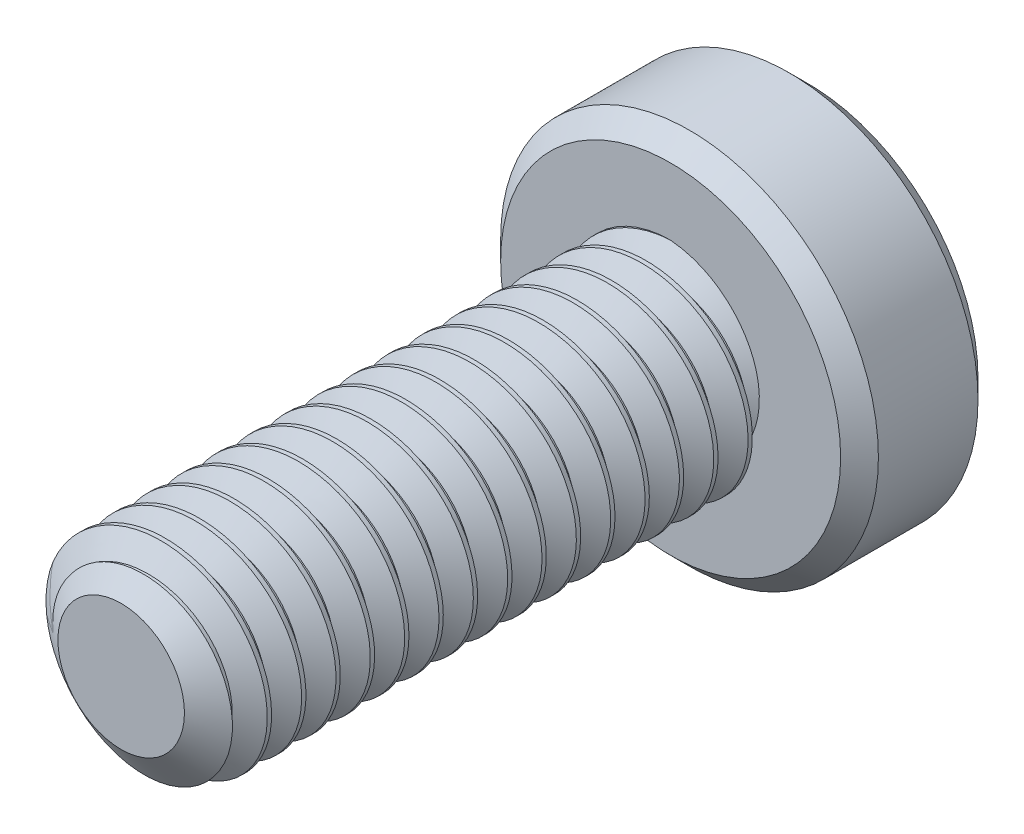
SolidWorks part; units mm, degrees
other "DetailItem1"
ref_plane "Front Plane" through (0, 0, 0) normal (0, 0, 1) x (1, 0, 0)
ref_plane "Top Plane" through (0, 0, 0) normal (0, 1, 0) x (1, 0, 0)
ref_plane "Right Plane" through (0, 0, 0) normal (1, 0, 0) x (0, 0, -1)
sketch "Sketch1" plane through (0, 0, 0) normal (0, 0, 1) x (1, 0, 0)
  circle A0 centre (0, 0) radius 1.5
  dimension "OD" = 3
extrude "Extrude1" add sketch "Sketch1" against normal blind 8
sketch "Sketch2" plane through (0, 0, 0) normal (0, 0, 1) x (1, 0, 0)
  circle A0 centre (0, 0) radius 1.5 construction
  circle A1 centre (0, 0) radius 1.5
curve "Helix/Spiral1" pitch 0.5 height 8.5 radius 1.5 centre (0, 0, 0) axis (0, 0, -1) start towards (0, 1, 0) parameters "pitch"=0.5
sketch "Sketch3" plane through (0, 0, 0) normal (1, 0, 0) x (0, 0, -1)
  line L0 (-0.4375, 1.5) -> (-0.25, 1.1752)
  line L1 (-0.25, 1.1752) -> (-0.1875, 1.1752)
  line L2 (-0.1875, 1.1752) -> (0, 1.5)
  line L3 (-0.4375, 1.5) -> (0, 1.5)
  line L4 (-0.2188, 1.5) -> (-0.2188, 1.1752) construction
  line L5 (-0.3438, 1.3376) -> (-0.0938, 1.3376) construction
  line L6 (0, 1.5) -> (0, -1.5) construction
  dimension "D1" = 0.0625
  dimension "D2" = 0.25
  dimension "D3" = 60
sweep "Cut-Sweep1" cut profiles "Sketch3" path "Helix/Spiral1" align with end faces yes
sketch "Sketch4" plane through (0, 0, 0) normal (1, 0, 0) x (0, 0, -1)
  line L0 (0.4053, 1.5) -> (0, 0.9212)
  line L1 (0, 0.9212) -> (0, 1.5)
  line L2 (0.4053, 1.5) -> (0, 1.5)
  line L3 (-0.4375, 1.5) -> (0, 1.5) construction
  line L4 (0, 0) -> (7.0209, 0) construction
  dimension "D1" = 55
  dimension "D2" = 0.254
revolve "Cut-Revolve1" cut sketch "Sketch4" angle 360 about L4
sketch "Sketch6" plane through (0, 0, -8) normal (0, 0, -1) x (-1, 0, 0)
  circle A0 centre (0, 0) radius 2.75
  dimension "head dia" = 5.5
extrude "Extrude2" add sketch "Sketch6" along normal blind 2
sketch "Sketch7" plane through (0, 0, -10) normal (0, 0, -1) x (-1, 0, 0)
  line L1 (0, 1.1547) -> (-1, 0.5774)
  line L2 (-1, 0.5774) -> (-1, -0.5774)
  line L3 (-1, -0.5774) -> (0, -1.1547)
  line L4 (0, -1.1547) -> (1, -0.5774)
  line L5 (1, -0.5774) -> (1, 0.5774)
  line L6 (1, 0.5774) -> (0, 1.1547)
  circle A0 centre (0, 0) radius 1 construction
  dimension "hex dia" = 2
extrude "Cut-Extrude1" cut sketch "Sketch7" against normal blind 1.5
sketch "Sketch8" plane through (0, 0, -10) normal (0, 0, -1) x (-1, 0, 0)
  circle A0 centre (0, 0) radius 1.1547
extrude "Cut-Extrude2" cut sketch "Sketch8" against normal through all draft 45
chamfer "Chamfer1" distance 0.275 angle 45 2 edges at (-2.75, 0, -10) (-2.75, 0, -8)
sketch "Sketch10" plane through (0, 0, -8) normal (0, 0, 1) x (1, 0, 0)
  circle A1 centre (0, 0) radius 1.5
  circle A2 centre (0, 0) radius 1.5
  dimension "D1" = 0
ref_plane "Plane1" through (0, 0, -30) normal (0, 0, 1) x (1, 0, 0)
extrude "partial thread" [suppressed] add sketch "Sketch10" along normal up to surface (20 mm away) separate body up to plane "Plane1"
chamfer "Chamfer2" [suppressed] distance 0.06 angle 45
combine bodies "Combine1" [suppressed] operation type add bodies to combine 107 108
sketch "Sketch9" plane through (0, 0, 0) normal (1, 0, 0) x (0, 0, -1)
  line L0 (0, 1.5) -> (0, -1.5) construction
  line L1 (1.25, 1.5) -> (1.25, -1.5) construction
  dimension "D1" = 1.25
equation "\"D3@Helix/Spiral1\" = \"screw length@Extrude1\"+\"pitch@Helix/Spiral1\""
equation "\"D1@Sketch3\" = \"pitch@Helix/Spiral1\"*.125"
equation "\"D2@Sketch3\" = \"pitch@Helix/Spiral1\"*.5"
equation "\"D1@Cut-Extrude1\" = \"hex dia@Sketch7\"*.75"
equation "\"D1@Chamfer1\" = \"head dia@Sketch6\"*.05"
equation "\"D1@Sketch9\" = \"pitch@Helix/Spiral1\"*2.5"
equation "\"D1@Chamfer2\"=\"OD@Sketch1\"*.02"
